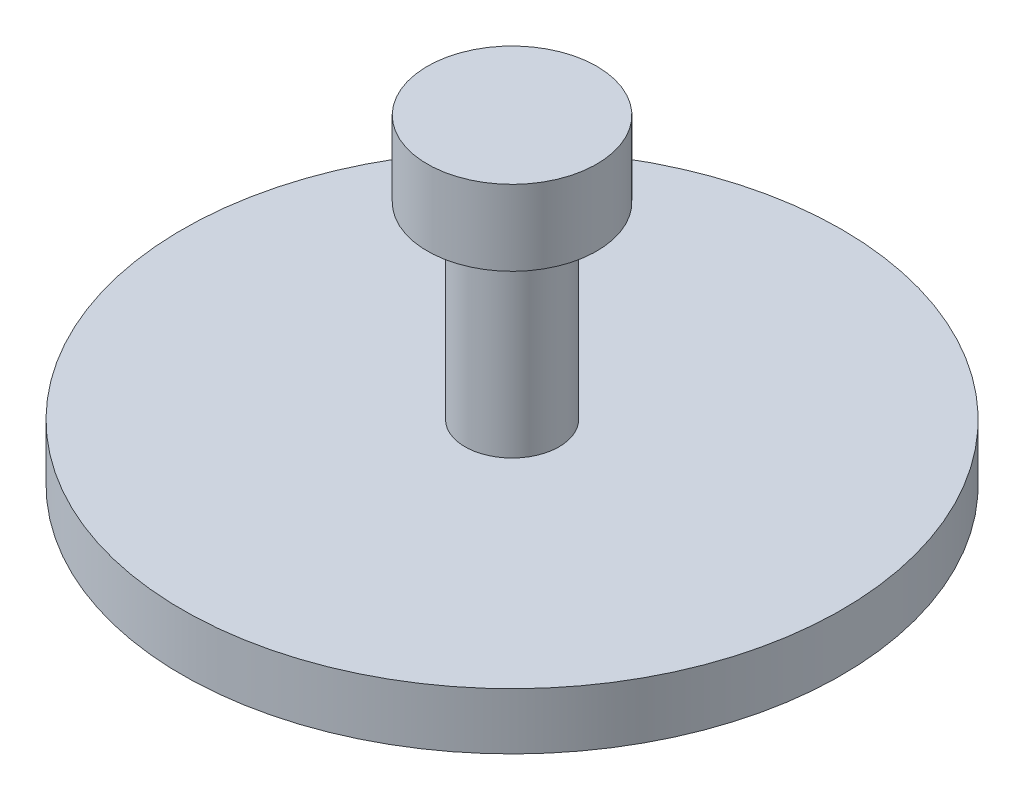
SolidWorks part; units mm, degrees
material "Plain Carbon Steel"
ref_plane "Front Plane" through (0, 0, 0) normal (0, 0, 1) x (1, 0, 0)
ref_plane "Top Plane" through (0, 0, 0) normal (0, 1, 0) x (1, 0, 0)
ref_plane "Right Plane" through (0, 0, 0) normal (1, 0, 0) x (0, 0, -1)
sketch "Sketch1" plane through (0, 0, 0) normal (0, 0, 1) x (1, 0, 0)
  line L0 (0, 0) -> (0, 17) construction
  line L1 (0, 0) -> (17.5, 0)
  line L2 (17.5, 0) -> (17.5, 3)
  line L3 (17.5, 3) -> (2.5, 3)
  line L4 (2.5, 3) -> (2.5, 13)
  line L5 (2.5, 13) -> (4.5, 13)
  line L6 (4.5, 13) -> (4.5, 17)
  line L7 (4.5, 17) -> (0, 17)
  line L8 (0, 17) -> (0, 0)
  dimension "D1" = 17.5
  dimension "D2" = 3
  dimension "D3" = 15
  dimension "D4" = 10
  dimension "D5" = 2
  dimension "D6" = 4
revolve "Revolve1" add sketch "Sketch1" angle 360 about L0
ref_axis "Axis1" through (0, 17.85, 0) along (0, -1, 0)
